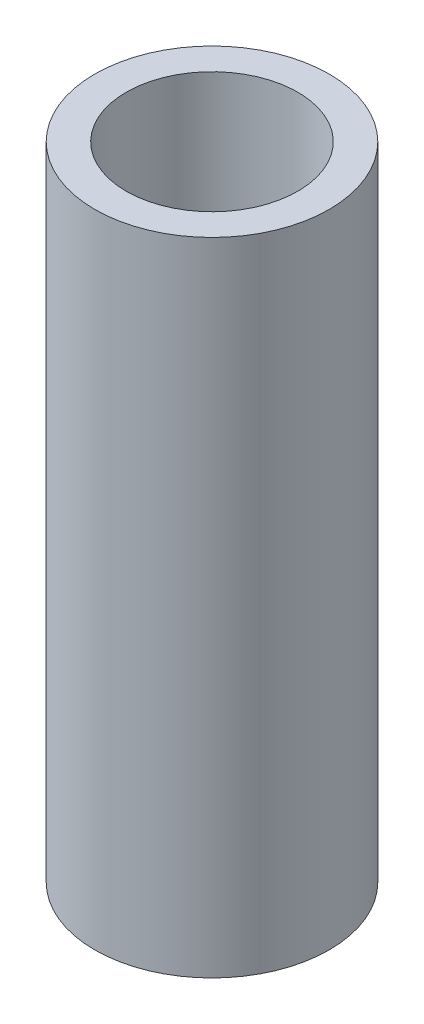
SolidWorks part; units mm, degrees
ref_plane "Front Plane" through (0, 0, 0) normal (0, 0, 1) x (1, 0, 0)
ref_plane "Top Plane" through (0, 0, 0) normal (0, 1, 0) x (1, 0, 0)
ref_plane "Right Plane" through (0, 0, 0) normal (1, 0, 0) x (0, 0, -1)
sketch "Sketch1" plane through (0, 0, 0) normal (0, 1, 0) x (1, 0, 0)
  circle A0 centre (0, 0) radius 30
  dimension "SLEEVE_OD" = 60
extrude "Boss-Extrude1" add sketch "Sketch1" along normal blind 164.1006
sketch "Sketch2" plane through (0, 0, 0) normal (0, 1, 0) x (1, 0, 0)
  circle A0 centre (0, 0) radius 21.9543
  dimension "BORE_D" = 43.9086
extrude "Cut-Extrude1" cut sketch "Sketch2" along normal through all
chamfer "Chamfer1" distance 3.8688 angle 48.614 rebuild error yes
